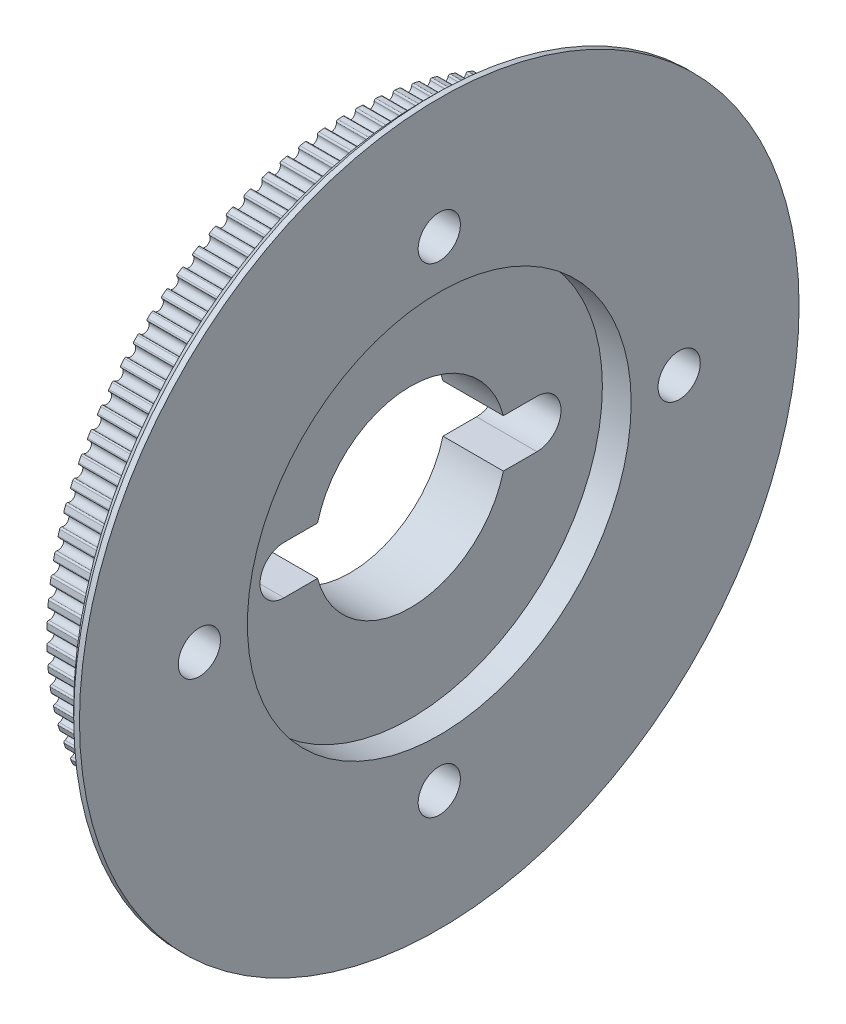
SolidWorks part; units mm, degrees
ref_plane "Front Plane" through (0, 0, 0) normal (0, 0, 1) x (1, 0, 0)
ref_plane "Top Plane" through (0, 0, 0) normal (0, 1, 0) x (1, 0, 0)
ref_plane "Right Plane" through (0, 0, 0) normal (1, 0, 0) x (0, 0, -1)
sketch "Sketch1" plane through (0, 0, 0) normal (1, 0, 0) x (0, 0, -1)
  circle A0 centre (0, 0) radius 31.6
  circle A1 centre (0, 0) radius 10
  dimension "D1" = 63.2
  dimension "D2" = 20
extrude "Boss-Extrude1" add sketch "Sketch1" along normal blind 7.7
sketch "Sketch2" plane through (0, 0, 0) normal (1, 0, 0) x (0, 0, -1)
  circle A0 centre (0, 0) radius 31.39 construction
  circle A1 centre (0, 31.39) radius 0.55
  circle A2 centre (0, 0) radius 31.39 construction
  circle A3 centre (1.971, 31.3281) radius 0.55
  circle A4 centre (0, 0) radius 31.39 construction
  circle A5 centre (3.9342, 31.1425) radius 0.55
  circle A6 centre (0, 0) radius 31.39 construction
  circle A7 centre (5.8819, 30.834) radius 0.55
  circle A8 centre (0, 0) radius 31.39 construction
  circle A9 centre (7.8064, 30.4038) radius 0.55
  circle A10 centre (0, 0) radius 31.39 construction
  circle A11 centre (9.7, 29.8537) radius 0.55
  circle A12 centre (0, 0) radius 31.39 construction
  circle A13 centre (11.5554, 29.1857) radius 0.55
  circle A14 centre (0, 0) radius 31.39 construction
  circle A15 centre (13.3652, 28.4025) radius 0.55
  circle A16 centre (0, 0) radius 31.39 construction
  circle A17 centre (15.1222, 27.5073) radius 0.55
  circle A18 centre (0, 0) radius 31.39 construction
  circle A19 centre (16.8196, 26.5035) radius 0.55
  circle A20 centre (0, 0) radius 31.39 construction
  circle A21 centre (18.4506, 25.395) radius 0.55
  circle A22 centre (0, 0) radius 31.39 construction
  circle A23 centre (20.0087, 24.1864) radius 0.55
  circle A24 centre (0, 0) radius 31.39 construction
  circle A25 centre (21.4879, 22.8823) radius 0.55
  circle A26 centre (0, 0) radius 31.39 construction
  circle A27 centre (22.8823, 21.4879) radius 0.55
  circle A28 centre (0, 0) radius 31.39 construction
  circle A29 centre (24.1864, 20.0087) radius 0.55
  circle A30 centre (0, 0) radius 31.39 construction
  circle A31 centre (25.395, 18.4506) radius 0.55
  circle A32 centre (0, 0) radius 31.39 construction
  circle A33 centre (26.5035, 16.8196) radius 0.55
  circle A34 centre (0, 0) radius 31.39 construction
  circle A35 centre (27.5073, 15.1222) radius 0.55
  circle A36 centre (0, 0) radius 31.39 construction
  circle A37 centre (28.4025, 13.3652) radius 0.55
  circle A38 centre (0, 0) radius 31.39 construction
  circle A39 centre (29.1857, 11.5554) radius 0.55
  circle A40 centre (0, 0) radius 31.39 construction
  circle A41 centre (29.8537, 9.7) radius 0.55
  circle A42 centre (0, 0) radius 31.39 construction
  circle A43 centre (30.4038, 7.8064) radius 0.55
  circle A44 centre (0, 0) radius 31.39 construction
  circle A45 centre (30.834, 5.8819) radius 0.55
  circle A46 centre (0, 0) radius 31.39 construction
  circle A47 centre (31.1425, 3.9342) radius 0.55
  circle A48 centre (0, 0) radius 31.39 construction
  circle A49 centre (31.3281, 1.971) radius 0.55
  circle A50 centre (0, 0) radius 31.39 construction
  circle A51 centre (31.39, 0) radius 0.55
  circle A52 centre (0, 0) radius 31.39 construction
  circle A53 centre (31.3281, -1.971) radius 0.55
  circle A54 centre (0, 0) radius 31.39 construction
  circle A55 centre (31.1425, -3.9342) radius 0.55
  circle A56 centre (0, 0) radius 31.39 construction
  circle A57 centre (30.834, -5.8819) radius 0.55
  circle A58 centre (0, 0) radius 31.39 construction
  circle A59 centre (30.4038, -7.8064) radius 0.55
  circle A60 centre (0, 0) radius 31.39 construction
  circle A61 centre (29.8537, -9.7) radius 0.55
  circle A62 centre (0, 0) radius 31.39 construction
  circle A63 centre (29.1857, -11.5554) radius 0.55
  circle A64 centre (0, 0) radius 31.39 construction
  circle A65 centre (28.4025, -13.3652) radius 0.55
  circle A66 centre (0, 0) radius 31.39 construction
  circle A67 centre (27.5073, -15.1222) radius 0.55
  circle A68 centre (0, 0) radius 31.39 construction
  circle A69 centre (26.5035, -16.8196) radius 0.55
  circle A70 centre (0, 0) radius 31.39 construction
  circle A71 centre (25.395, -18.4506) radius 0.55
  circle A72 centre (0, 0) radius 31.39 construction
  circle A73 centre (24.1864, -20.0087) radius 0.55
  circle A74 centre (0, 0) radius 31.39 construction
  circle A75 centre (22.8823, -21.4879) radius 0.55
  circle A76 centre (0, 0) radius 31.39 construction
  circle A77 centre (21.4879, -22.8823) radius 0.55
  circle A78 centre (0, 0) radius 31.39 construction
  circle A79 centre (20.0087, -24.1864) radius 0.55
  circle A80 centre (0, 0) radius 31.39 construction
  circle A81 centre (18.4506, -25.395) radius 0.55
  circle A82 centre (0, 0) radius 31.39 construction
  circle A83 centre (16.8196, -26.5035) radius 0.55
  circle A84 centre (0, 0) radius 31.39 construction
  circle A85 centre (15.1222, -27.5073) radius 0.55
  circle A86 centre (0, 0) radius 31.39 construction
  circle A87 centre (13.3652, -28.4025) radius 0.55
  circle A88 centre (0, 0) radius 31.39 construction
  circle A89 centre (11.5554, -29.1857) radius 0.55
  circle A90 centre (0, 0) radius 31.39 construction
  circle A91 centre (9.7, -29.8537) radius 0.55
  circle A92 centre (0, 0) radius 31.39 construction
  circle A93 centre (7.8064, -30.4038) radius 0.55
  circle A94 centre (0, 0) radius 31.39 construction
  circle A95 centre (5.8819, -30.834) radius 0.55
  circle A96 centre (0, 0) radius 31.39 construction
  circle A97 centre (3.9342, -31.1425) radius 0.55
  circle A98 centre (0, 0) radius 31.39 construction
  circle A99 centre (1.971, -31.3281) radius 0.55
  circle A100 centre (0, 0) radius 31.39 construction
  circle A101 centre (0, -31.39) radius 0.55
  circle A102 centre (0, 0) radius 31.39 construction
  circle A103 centre (-1.971, -31.3281) radius 0.55
  circle A104 centre (0, 0) radius 31.39 construction
  circle A105 centre (-3.9342, -31.1425) radius 0.55
  circle A106 centre (0, 0) radius 31.39 construction
  circle A107 centre (-5.8819, -30.834) radius 0.55
  circle A108 centre (0, 0) radius 31.39 construction
  circle A109 centre (-7.8064, -30.4038) radius 0.55
  circle A110 centre (0, 0) radius 31.39 construction
  circle A111 centre (-9.7, -29.8537) radius 0.55
  circle A112 centre (0, 0) radius 31.39 construction
  circle A113 centre (-11.5554, -29.1857) radius 0.55
  circle A114 centre (0, 0) radius 31.39 construction
  circle A115 centre (-13.3652, -28.4025) radius 0.55
  circle A116 centre (0, 0) radius 31.39 construction
  circle A117 centre (-15.1222, -27.5073) radius 0.55
  circle A118 centre (0, 0) radius 31.39 construction
  circle A119 centre (-16.8196, -26.5035) radius 0.55
  circle A120 centre (0, 0) radius 31.39 construction
  circle A121 centre (-18.4506, -25.395) radius 0.55
  circle A122 centre (0, 0) radius 31.39 construction
  circle A123 centre (-20.0087, -24.1864) radius 0.55
  circle A124 centre (0, 0) radius 31.39 construction
  circle A125 centre (-21.4879, -22.8823) radius 0.55
  circle A126 centre (0, 0) radius 31.39 construction
  circle A127 centre (-22.8823, -21.4879) radius 0.55
  circle A128 centre (0, 0) radius 31.39 construction
  circle A129 centre (-24.1864, -20.0087) radius 0.55
  circle A130 centre (0, 0) radius 31.39 construction
  circle A131 centre (-25.395, -18.4506) radius 0.55
  circle A132 centre (0, 0) radius 31.39 construction
  circle A133 centre (-26.5035, -16.8196) radius 0.55
  circle A134 centre (0, 0) radius 31.39 construction
  circle A135 centre (-27.5073, -15.1222) radius 0.55
  circle A136 centre (0, 0) radius 31.39 construction
  circle A137 centre (-28.4025, -13.3652) radius 0.55
  circle A138 centre (0, 0) radius 31.39 construction
  circle A139 centre (-29.1857, -11.5554) radius 0.55
  circle A140 centre (0, 0) radius 31.39 construction
  circle A141 centre (-29.8537, -9.7) radius 0.55
  circle A142 centre (0, 0) radius 31.39 construction
  circle A143 centre (-30.4038, -7.8064) radius 0.55
  circle A144 centre (0, 0) radius 31.39 construction
  circle A145 centre (-30.834, -5.8819) radius 0.55
  circle A146 centre (0, 0) radius 31.39 construction
  circle A147 centre (-31.1425, -3.9342) radius 0.55
  circle A148 centre (0, 0) radius 31.39 construction
  circle A149 centre (-31.3281, -1.971) radius 0.55
  circle A150 centre (0, 0) radius 31.39 construction
  circle A151 centre (-31.39, 0) radius 0.55
  circle A152 centre (0, 0) radius 31.39 construction
  circle A153 centre (-31.3281, 1.971) radius 0.55
  circle A154 centre (0, 0) radius 31.39 construction
  circle A155 centre (-31.1425, 3.9342) radius 0.55
  circle A156 centre (0, 0) radius 31.39 construction
  circle A157 centre (-30.834, 5.8819) radius 0.55
  circle A158 centre (0, 0) radius 31.39 construction
  circle A159 centre (-30.4038, 7.8064) radius 0.55
  circle A160 centre (0, 0) radius 31.39 construction
  circle A161 centre (-29.8537, 9.7) radius 0.55
  circle A162 centre (0, 0) radius 31.39 construction
  circle A163 centre (-29.1857, 11.5554) radius 0.55
  circle A164 centre (0, 0) radius 31.39 construction
  circle A165 centre (-28.4025, 13.3652) radius 0.55
  circle A166 centre (0, 0) radius 31.39 construction
  circle A167 centre (-27.5073, 15.1222) radius 0.55
  circle A168 centre (0, 0) radius 31.39 construction
  circle A169 centre (-26.5035, 16.8196) radius 0.55
  circle A170 centre (0, 0) radius 31.39 construction
  circle A171 centre (-25.395, 18.4506) radius 0.55
  circle A172 centre (0, 0) radius 31.39 construction
  circle A173 centre (-24.1864, 20.0087) radius 0.55
  circle A174 centre (0, 0) radius 31.39 construction
  circle A175 centre (-22.8823, 21.4879) radius 0.55
  circle A176 centre (0, 0) radius 31.39 construction
  circle A177 centre (-21.4879, 22.8823) radius 0.55
  circle A178 centre (0, 0) radius 31.39 construction
  circle A179 centre (-20.0087, 24.1864) radius 0.55
  circle A180 centre (0, 0) radius 31.39 construction
  circle A181 centre (-18.4506, 25.395) radius 0.55
  circle A182 centre (0, 0) radius 31.39 construction
  circle A183 centre (-16.8196, 26.5035) radius 0.55
  circle A184 centre (0, 0) radius 31.39 construction
  circle A185 centre (-15.1222, 27.5073) radius 0.55
  circle A186 centre (0, 0) radius 31.39 construction
  circle A187 centre (-13.3652, 28.4025) radius 0.55
  circle A188 centre (0, 0) radius 31.39 construction
  circle A189 centre (-11.5554, 29.1857) radius 0.55
  circle A190 centre (0, 0) radius 31.39 construction
  circle A191 centre (-9.7, 29.8537) radius 0.55
  circle A192 centre (0, 0) radius 31.39 construction
  circle A193 centre (-7.8064, 30.4038) radius 0.55
  circle A194 centre (0, 0) radius 31.39 construction
  circle A195 centre (-5.8819, 30.834) radius 0.55
  circle A196 centre (0, 0) radius 31.39 construction
  circle A197 centre (-3.9342, 31.1425) radius 0.55
  circle A198 centre (0, 0) radius 31.39 construction
  circle A199 centre (-1.971, 31.3281) radius 0.55
  point P305 (0, 0)
  dimension "D1" = 62.78
  dimension "D2" = 1.1
  dimension "D3" = 100
extrude "Cut-Extrude1" cut sketch "Sketch2" along normal up to surface (7.7 mm away) up to face at (7.7, 0, -31.6)
fillet "Fillet1" radius 0.16 200 edges at (3.85, 31.5959, 0.51) (3.85, 31.5656, 1.4749) (3.85, 21.2571, -23.3815) (3.85, 22.6833, -22.0007) (3.85, 22.0007, -22.6833) (3.85, 20.5329, -24.02) (3.85, 19.747, -24.6701) (3.85, 18.9842, -25.2618) (3.85, 18.159, -25.8614) (3.85, 17.3605, -26.404) (3.85, 16.4993, -26.9506) (3.85, 15.6684, -27.442) (3.85, 14.7745, -27.9334) (3.85, 13.9143, -28.3717) (3.85, 12.9914, -28.806) (3.85, 12.1054, -29.1894) (3.85, 23.3815, -21.2571) (3.85, 24.02, -20.5329) (3.85, 24.6701, -19.747) (3.85, 25.2618, -18.9842) (3.85, 25.8614, -18.159) (3.85, 26.404, -17.3605) (3.85, 26.9506, -16.4993) (3.85, 27.442, -15.6684) (3.85, 27.9334, -14.7745) (3.85, 28.3717, -13.9143) (3.85, 28.806, -12.9914) (3.85, 29.1894, -12.1054) (3.85, 29.5649, -11.157) (3.85, 29.8919, -10.2487) (3.85, 30.2071, -9.2786) (3.85, 30.4764, -8.3516) (3.85, 30.7301, -7.3636) (3.85, 30.9407, -6.4215) (3.85, 31.1318, -5.4195) (3.85, 31.2828, -4.466) (3.85, 31.4107, -3.454) (3.85, 31.5015, -2.4929) (3.85, 31.5656, -1.4749) (3.85, 31.5959, -0.51) (3.85, 31.5015, 2.4929) (3.85, 31.4107, 3.454) (3.85, 31.2828, 4.466) (3.85, 31.1318, 5.4195) (3.85, 30.9407, 6.4215) (3.85, 30.7301, 7.3636) (3.85, 30.4764, 8.3516) (3.85, 30.2071, 9.2786) (3.85, 29.8919, 10.2487) (3.85, 29.5649, 11.157) (3.85, 29.1894, 12.1054) (3.85, 28.806, 12.9914) (3.85, 28.3717, 13.9143) (3.85, 27.9334, 14.7745) (3.85, 27.442, 15.6684) (3.85, 26.9506, 16.4993) (3.85, 26.404, 17.3605) (3.85, 25.8614, 18.159) (3.85, 25.2618, 18.9842) (3.85, 24.6701, 19.747) (3.85, 24.02, 20.5329) (3.85, 23.3815, 21.2571) (3.85, 22.6833, 22.0007) (3.85, 22.0007, 22.6833) (3.85, 21.2571, 23.3815) (3.85, 20.5329, 24.02) (3.85, 19.747, 24.6701) (3.85, 18.9842, 25.2618) (3.85, 18.159, 25.8614) (3.85, 17.3605, 26.404) (3.85, 16.4993, 26.9506) (3.85, 15.6684, 27.442) (3.85, 14.7745, 27.9334) (3.85, 13.9143, 28.3717) (3.85, 12.9914, 28.806) (3.85, 12.1054, 29.1894) (3.85, 11.157, 29.5649) (3.85, 10.2487, 29.8919) (3.85, 9.2786, 30.2071) (3.85, 8.3516, 30.4764) (3.85, 7.3636, 30.7301) (3.85, 6.4215, 30.9407) (3.85, 5.4195, 31.1318) (3.85, 4.466, 31.2828) (3.85, 3.454, 31.4107) (3.85, 2.4929, 31.5015) (3.85, 1.4749, 31.5656) (3.85, 0.51, 31.5959) (3.85, -0.51, 31.5959) (3.85, -1.4749, 31.5656) (3.85, -2.4929, 31.5015) (3.85, -3.454, 31.4107) (3.85, -4.466, 31.2828) (3.85, -5.4195, 31.1318) (3.85, -6.4215, 30.9407) (3.85, -7.3636, 30.7301) (3.85, -8.3516, 30.4764) (3.85, -9.2786, 30.2071) (3.85, -10.2487, 29.8919) (3.85, -11.157, 29.5649) (3.85, -12.1054, 29.1894) (3.85, -12.9914, 28.806) (3.85, -13.9143, 28.3717) (3.85, -14.7745, 27.9334) (3.85, -15.6684, 27.442) (3.85, -16.4993, 26.9506) (3.85, -17.3605, 26.404) (3.85, -18.159, 25.8614) (3.85, -18.9842, 25.2618) (3.85, -19.747, 24.6701) (3.85, -20.5329, 24.02) (3.85, -21.2571, 23.3815) (3.85, -22.0007, 22.6833) (3.85, -22.6833, 22.0007) (3.85, -23.3815, 21.2571) (3.85, -24.02, 20.5329) (3.85, -24.6701, 19.747) (3.85, -25.2618, 18.9842) (3.85, -25.8614, 18.159) (3.85, -26.404, 17.3605) (3.85, -26.9506, 16.4993) (3.85, -27.442, 15.6684) (3.85, -27.9334, 14.7745) (3.85, -28.3717, 13.9143) (3.85, -28.806, 12.9914) (3.85, -29.1894, 12.1054) (3.85, -29.5649, 11.157) (3.85, -29.8919, 10.2487) (3.85, -30.2071, 9.2786) (3.85, -30.4764, 8.3516) (3.85, -30.7301, 7.3636) (3.85, -30.9407, 6.4215) (3.85, -31.1318, 5.4195) (3.85, -31.2828, 4.466) (3.85, -31.4107, 3.454) (3.85, -31.5015, 2.4929) (3.85, -31.5656, 1.4749) (3.85, -31.5959, 0.51) (3.85, -31.5959, -0.51) (3.85, -31.5656, -1.4749) (3.85, -31.5015, -2.4929) (3.85, -31.4107, -3.454) (3.85, -31.2828, -4.466) (3.85, -31.1318, -5.4195) (3.85, -30.9407, -6.4215) (3.85, -30.7301, -7.3636) (3.85, -30.4764, -8.3516) (3.85, -30.2071, -9.2786) (3.85, -29.8919, -10.2487) (3.85, -29.5649, -11.157) (3.85, -29.1894, -12.1054) (3.85, -28.806, -12.9914) (3.85, -28.3717, -13.9143) (3.85, -27.9334, -14.7745) (3.85, -27.442, -15.6684) (3.85, -26.9506, -16.4993) (3.85, -26.404, -17.3605) (3.85, -25.8614, -18.159) (3.85, -25.2618, -18.9842) (3.85, -24.6701, -19.747) (3.85, -24.02, -20.5329) (3.85, -23.3815, -21.2571) (3.85, -22.6833, -22.0007) (3.85, -22.0007, -22.6833) (3.85, -21.2571, -23.3815) (3.85, -20.5329, -24.02) (3.85, -19.747, -24.6701) (3.85, -18.9842, -25.2618) (3.85, -18.159, -25.8614) (3.85, -17.3605, -26.404) (3.85, -16.4993, -26.9506) (3.85, -15.6684, -27.442) (3.85, -14.7745, -27.9334) (3.85, -13.9143, -28.3717) (3.85, -12.9914, -28.806) (3.85, -12.1054, -29.1894) (3.85, -11.157, -29.5649) (3.85, -10.2487, -29.8919) (3.85, -9.2786, -30.2071) (3.85, -8.3516, -30.4764) (3.85, -7.3636, -30.7301) (3.85, -6.4215, -30.9407) (3.85, -5.4195, -31.1318) (3.85, -4.466, -31.2828) (3.85, -3.454, -31.4107) (3.85, -2.4929, -31.5015) (3.85, 11.157, -29.5649) (3.85, 10.2487, -29.8919) (3.85, 9.2786, -30.2071) (3.85, 8.3516, -30.4764) (3.85, 7.3636, -30.7301) (3.85, 6.4215, -30.9407) (3.85, 5.4195, -31.1318) (3.85, 4.466, -31.2828) (3.85, 3.454, -31.4107) (3.85, 2.4929, -31.5015) (3.85, 1.4749, -31.5656) (3.85, 0.51, -31.5959) (3.85, -1.4749, -31.5656) (3.85, -0.51, -31.5959)
ref_axis "Axis1" through (7.7, 0, 0) along (-1, 0, 0)
sketch "Sketch3" plane through (7.7, 0, 0) normal (1, 0, 0) x (0, 0, -1)
  circle A0 centre (0, 0) radius 37.5
  circle A1 centre (0, 0) radius 10
  circle A2 centre (0, 0) radius 10 construction
  dimension "D1" = 75
extrude "Boss-Extrude2" add sketch "Sketch3" along normal blind 1.6
sketch "Sketch6" plane through (9.3, 0, 0) normal (1, 0, 0) x (0, 0, -1)
  circle A0 centre (0, -25) radius 2.2
  circle A3 centre (-25, 0) radius 2.2
  circle A4 centre (0, 25) radius 2.2
  circle A5 centre (25, 0) radius 2.2
  point P13 (0, 0)
  dimension "D1" = 4.4
  dimension "D2" = 25
  dimension "D3" = 4
extrude "Cut-Extrude6" cut sketch "Sketch6" against normal up to surface (9.3 mm away) up to face at (0, 0, 0)
chamfer "Chamfer1" distance 1 angle 45 1 edges at (7.7, 0, -37.5)
sketch "Sketch8" plane through (9.3, 0, 0) normal (1, 0, 0) x (0, 0, -1)
  circle A0 centre (0, 0) radius 20
  dimension "D1" = 40
extrude "Cut-Extrude7" cut sketch "Sketch8" against normal blind 3
sketch "Esquisse2" plane through (0, 0, 0) normal (-1, 0, 0) x (0, 0, 1)
  line L0 (-7.7811, 0) -> (39.7368, 0) construction
  line L3 (9.6825, -2.5) -> (13.1825, -2.5)
  line L4 (9.6825, 2.5) -> (13.1825, 2.5)
  line L5 (0, -12.2602) -> (0, 16.7447) construction
  line L6 (-9.6825, 2.5) -> (-13.1825, 2.5)
  line L7 (-9.6825, -2.5) -> (-13.1825, -2.5)
  circle A2 centre (0, 0) radius 10 construction
  arc A5 (13.1825, -2.5) -> (13.1825, 2.5) centre (13.1825, 0) ccw
  circle A6 centre (0, 0) radius 10
  arc A7 (-13.1825, -2.5) -> (-13.1825, 2.5) centre (-13.1825, 0) cw
  dimension "D1" = 3.5
  dimension "D2" = 2.5
extrude "Enlèv. mat.-Extru.2" cut sketch "Esquisse2" against normal blind 6.3 contours A6 L3 A5 L4 | A7 L7 A6 L6 region at (0, 0, 12.5492) region at (0, 0, -12.5492)
scale "Echelle1" bodies to scale 118 scale about centroid uniform scaling yes scale factor 2
scale "Echelle2" scale about centroid uniform scaling yes scale factor 0.25
